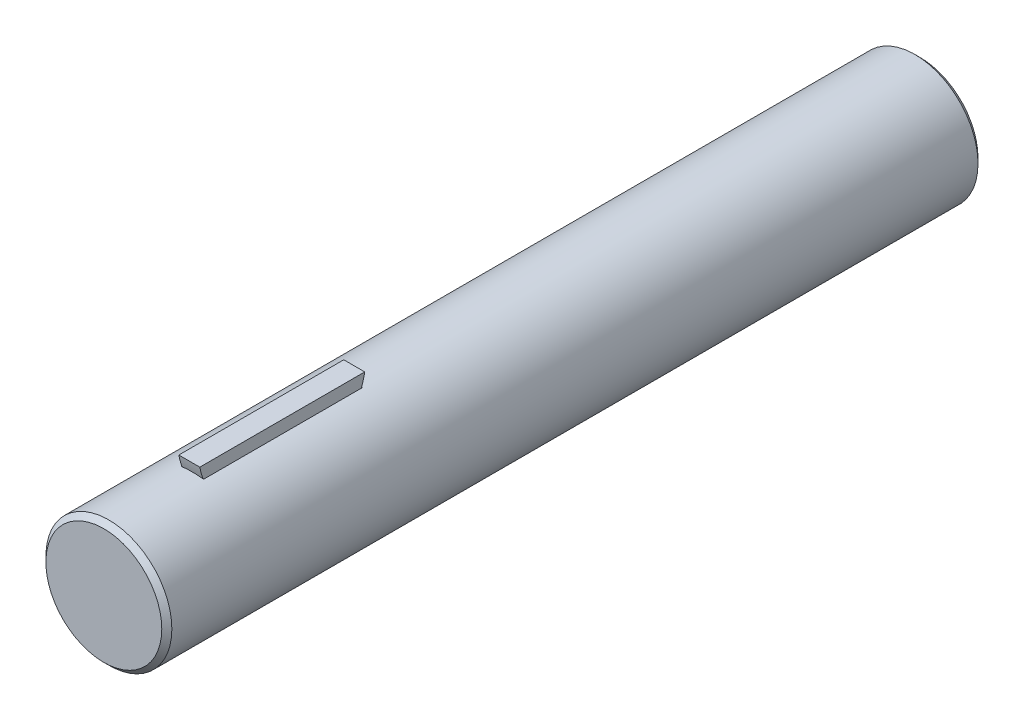
SolidWorks part; units mm, degrees
material "AISI 304"
ref_plane "Front Plane" through (0, 0, 0) normal (0, 0, 1) x (1, 0, 0)
ref_plane "Top Plane" through (0, 0, 0) normal (0, 1, 0) x (1, 0, 0)
ref_plane "Right Plane" through (0, 0, 0) normal (1, 0, 0) x (0, 0, -1)
sketch "Sketch1" plane through (0, 0, 0) normal (1, 0, 0) x (0, 0, -1)
  line L0 (-44.323, 0) -> (-44.323, 4.3815)
  line L1 (-44.323, 4.3815) -> (-43.942, 4.7625)
  line L2 (-43.942, 4.7625) -> (17.018, 4.7625)
  line L3 (17.018, 4.7625) -> (17.399, 4.3815)
  line L4 (17.399, 4.3815) -> (17.399, 0)
  line L5 (17.399, 0) -> (-44.323, 0)
  line L6 (17.399, 0) -> (-44.323, 0) construction
revolve "Revolve1" add sketch "Sketch1" angle 360 about L6 reverse direction yes
sketch "Sketch2" plane through (0, 0, 0) normal (1, 0, 0) x (0, 0, -1)
  line L0 (-25.3873, 5.5753) -> (-37.8587, 5.5753)
  arc A0 (-37.8587, 5.5753) -> (-25.3873, 5.5753) centre (-31.623, 6.7747) ccw
extrude "Cut-Extrude1" cut sketch "Sketch2" along normal blind 0.8446 and the other way blind 0.8446
ref_plane "Plane1" through (0, 5.9563, 0) normal (0, 1, 0) x (1, 0, 0)
ref_plane "Plane2" through (0, 0, 44.323) normal (0, 0, 1) x (1, 0, 0)
sketch "Sketch3" plane through (0, 0, 0) normal (1, 0, 0) x (0, 0, -1)
  line L0 (-31.75, 0.426) -> (-31.75, 0.1694)
  line L1 (-31.75, 0.1694) -> (-31.496, 0.1694)
  line L2 (-31.496, 0.1694) -> (-31.496, 0.426)
  line L3 (-25.3873, 5.5753) -> (-37.8587, 5.5753)
  arc A0 (-37.8587, 5.5753) -> (-31.75, 0.426) centre (-31.623, 6.7747) ccw
  arc A1 (-31.496, 0.426) -> (-25.3873, 5.5753) centre (-31.623, 6.7747) ccw
extrude "Boss-Extrude1" add sketch "Sketch3" against normal blind 0.7937 and the other way blind 0.7937
ref_plane "shaft XY" through (0, 0, 44.323) normal (0, 0, 1) x (1, 0, 0)
ref_plane "shaft XZ" through (0, 0, 0) normal (0, -1, 0) x (-1, 0, 0)
ref_plane "shaft YZ" through (0, 0, 0) normal (1, 0, 0) x (0, 0, -1)
ref_axis "shaft X" through (-80.9, 0, 44.323) along (1, 0, 0)
ref_axis "shaft Y" through (0, -50, 44.323) along (0, 1, 0)
ref_axis "shaft Z" through (0, 0, 80.9) along (0, 0, -1)
sketch3d "shaft"
  point P0 (0, 0, 44.323)
